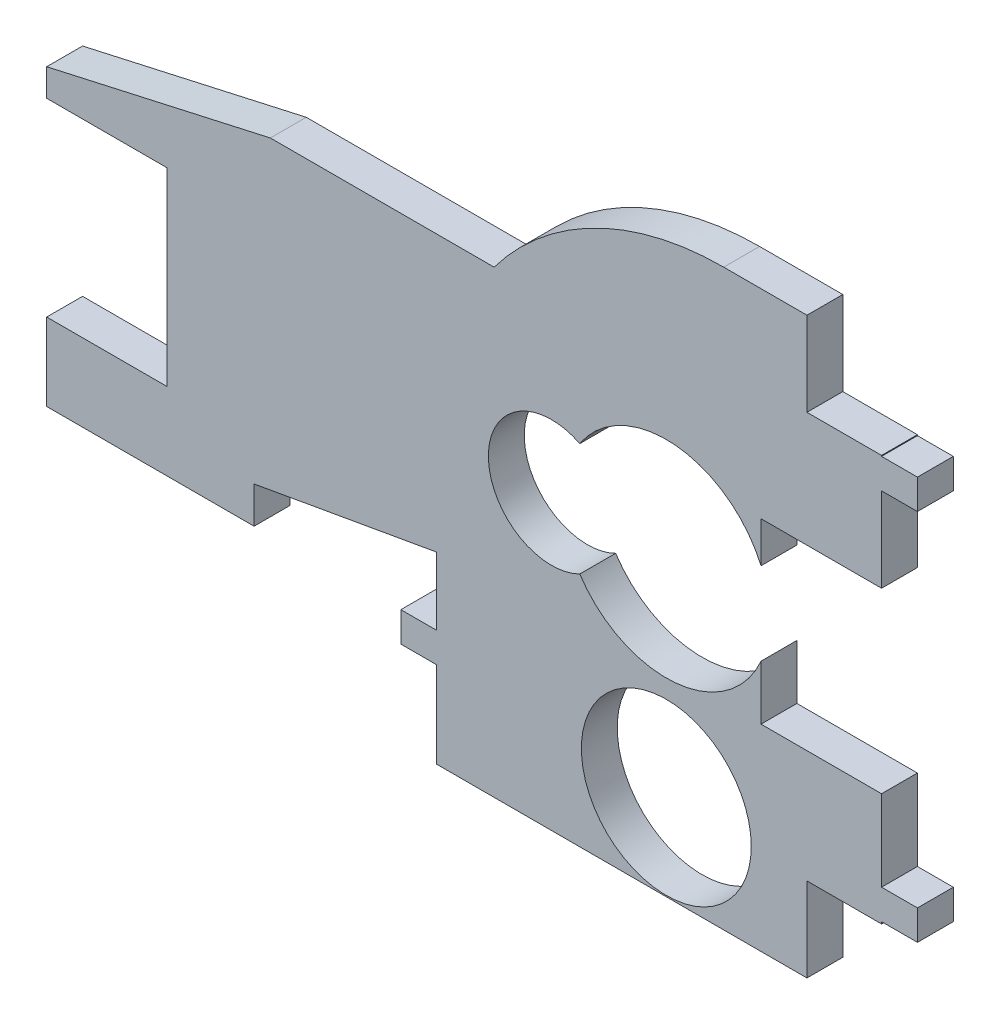
SolidWorks part; units mm, degrees
material "Balsa"
ref_plane "Front Plane" through (0, 0, 0) normal (0, 0, 1) x (1, 0, 0)
ref_plane "Top Plane" through (0, 0, 0) normal (0, 1, 0) x (1, 0, 0)
ref_plane "Right Plane" through (0, 0, 0) normal (1, 0, 0) x (0, 0, -1)
sketch "Sketch1" plane through (0, 0, 0) normal (0, 0, 1) x (1, 0, 0)
  line L0 (0, -1000.1535) -> (0, 48999.8465) construction
  line L1 (0, 9.144) -> (-5.08, 9.144) construction
  line L2 (-1000, 0) -> (49000, 0) construction
  line L3 (9.525, 16.51) -> (11.1125, 16.51)
  line L4 (2.54, 21.59) -> (9.525, 21.59)
  line L5 (-10.16, 8.89) -> (-10.16, -3.81)
  line L6 (-10.16, -3.81) -> (9.525, -3.81)
  line L7 (9.525, 21.59) -> (9.525, -3.81)
  line L8 (-11.7475, 0) -> (-10.16, 0)
  line L9 (-11.7475, 0) -> (-11.7475, 1.3208)
  line L10 (-11.7475, 1.3208) -> (-10.16, 1.3208)
  line L11 (-10.16, 0) -> (-10.16, 1.3208)
  line L12 (9.525, 0) -> (11.1125, 0)
  line L13 (9.525, 0) -> (9.525, 1.3208)
  line L14 (9.525, 1.3208) -> (11.1125, 1.3208)
  line L15 (11.1125, 0) -> (11.1125, 1.3208)
  line L16 (9.525, 16.51) -> (9.525, 17.8308)
  line L17 (9.525, 17.8308) -> (11.1125, 17.8308)
  line L18 (11.1125, 16.51) -> (11.1125, 17.8308)
  line L19 (-7.62, 16.51) -> (-27.4189, 16.51)
  line L20 (-27.4189, 16.51) -> (-27.4189, 1.27)
  line L21 (-27.4189, 1.27) -> (-10.16, 4.318)
  line L22 (9.525, 8.89) -> (-35.5862, 8.89) construction
  line L23 (-27.4189, 1.27) -> (-18.2418, 1.27)
  line L24 (-27.4189, 13.081) -> (-22.0849, 13.081)
  line L25 (-27.4189, 13.081) -> (-27.4189, 4.699)
  line L26 (-27.4189, 4.699) -> (-22.0849, 4.699)
  line L27 (-22.0849, 13.081) -> (-22.0849, 4.699)
  line L28 (-18.2418, 1.27) -> (-18.2418, 2.8907)
  line L29 (-27.4189, 14.2918) -> (-17.5195, 16.51)
  line L30 (9.525, 12.7762) -> (4.191, 12.7762)
  line L31 (9.525, 12.7762) -> (9.525, 4.9022)
  line L32 (9.525, 4.9022) -> (4.191, 4.9022)
  line L33 (4.191, 12.7762) -> (4.191, 4.9022)
  circle A0 centre (0, 0) radius 3.7592
  arc A1 (-3.829, 6.6457) -> (-3.829, 11.6423) centre (0, 9.144) ccw
  arc A2 (-3.829, 11.6423) -> (-3.829, 6.6457) centre (-5.08, 9.144) ccw
  arc A3 (2.54, 21.59) -> (-10.16, 8.89) centre (2.54, 8.89) ccw
  point P33 (9.525, 8.89)
  point P35 (-27.4189, 8.89)
  point P41 (-27.4189, 8.89)
  dimension "D1" = 7.5184
  dimension "D4" = 3.81
  dimension "D3" = 9.144
  dimension "D5" = 2.794
  dimension "D9" = 12.7
  dimension "D10" = 1.5875
  dimension "D2" = 25.4
  dimension "D6" = 9.525
  dimension "D7" = 5.08
  dimension "D8" = 19.685
  dimension "D11" = 9.144
  dimension "D12" = 1.3208
  dimension "D13" = 1.3208
  dimension "D14" = 1.5875
  dimension "D15" = 2
  dimension "D16" = 8.128
  dimension "D17" = 15.24
  dimension "D18" = 17.526
  dimension "D19" = 8.382
  dimension "D20" = 5.334
  dimension "D21" = 5.334
  dimension "D22" = 8.8138
  dimension "D23" = 7.874
  dimension "D24" = 2.2182
extrude "Boss-Extrude1" add sketch "Sketch1" along normal blind 1.5875 contours L4 A3 L5 L6 L7 A0 A2 A1 | L10 L9 L8 L5 | L3 L18 L17 L7 | L12 L15 L14 L7 | A3 L19 L20 L21 L5 | L23 L28 L21 region at (10.3187, 17.1704, 0) region at (9.2036, 14.6431, 0) region at (10.3187, 0.6604, 0) region at (-17.148, 9.604, 0) region at (-10.9538, 0.6604, 0) region at (-21.3008, 1.8102, 0)
sketch "Sketch2" plane through (0, 0, 1.5875) normal (0, 0, 1) x (1, 0, 0)
  line L1 (6.223, -3.8481) -> (9.525, -3.8481)
  line L2 (6.223, -3.8481) -> (6.223, -0.0889)
  line L3 (6.223, -0.0889) -> (9.525, -0.0889)
  line L4 (9.525, -3.8481) -> (9.525, -0.0889)
  line L5 (9.525, -0.9144) -> (9.525, -3.0226)
  line L7 (9.525, 20.8026) -> (9.525, 18.6944)
  line L9 (6.223, 17.8689) -> (9.525, 17.8689)
  line L10 (6.223, 17.8689) -> (6.223, 21.6281)
  line L11 (6.223, 21.6281) -> (9.525, 21.6281)
  line L12 (9.525, 17.8689) -> (9.525, 21.6281)
  point P8 (9.525, -1.9685)
  point P9 (9.525, -1.9685)
  point P10 (9.525, 19.7485)
  point P15 (9.525, 19.7485)
  line M4 (9.525, 21.59) -> (2.54, 21.59)
  line M11 (-10.16, -3.81) -> (9.525, -3.81)
  line M12 (9.525, -3.81) -> (9.525, 0)
  dimension "D1" = 3.7592
  dimension "D2" = 3.302
  dimension "D3" = 3.7592
  dimension "D4" = 3.302
extrude "Cut-Extrude1" cut sketch "Sketch2" against normal up to next contours L3 L2 L4 M11 M12 | L10 L9 M4 region at (7.874, -1.9495, 1.5875) region at (7.874, 19.7294, 1.5875)
move or copy body "Body-Move/Copy1" [suppressed] bodies to move or copy 102
